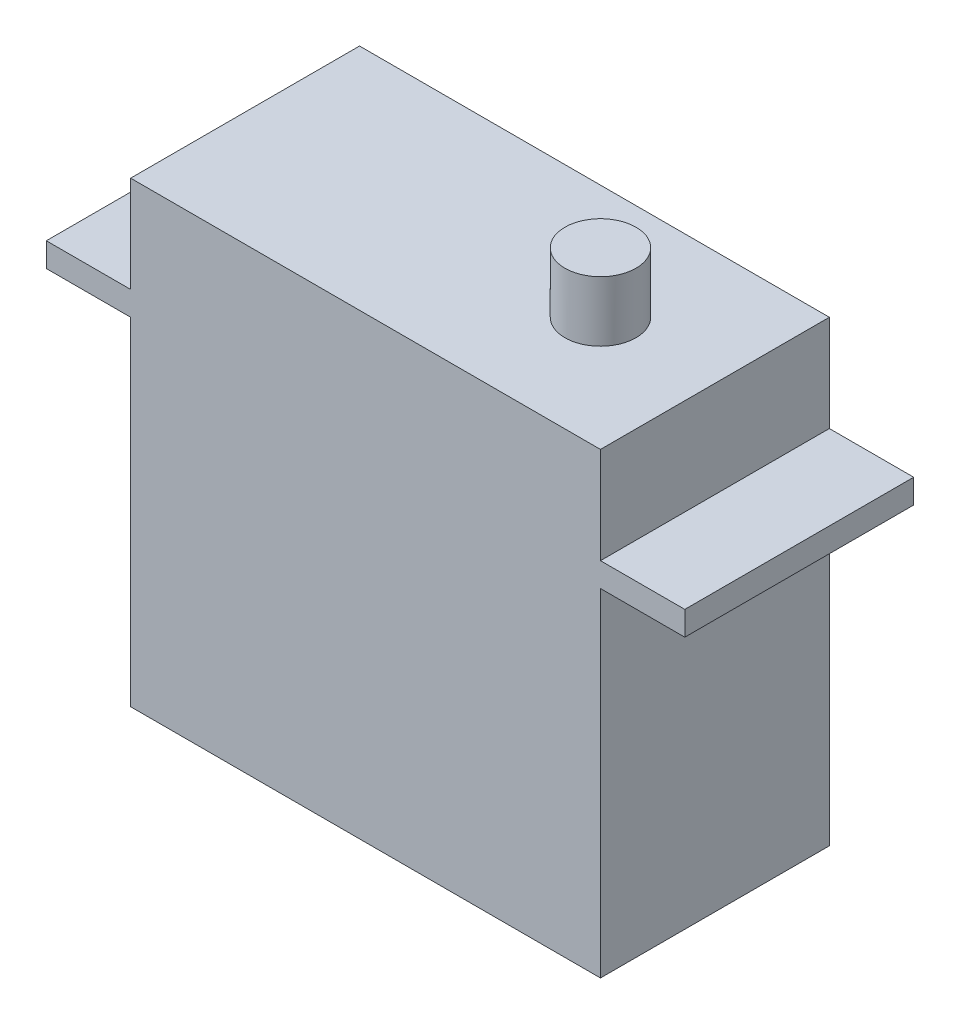
SolidWorks part; units mm, degrees
ref_plane "Plan de face" through (0, 0, 0) normal (0, 0, 1) x (1, 0, 0)
ref_plane "Plan de dessus" through (0, 0, 0) normal (0, 1, 0) x (1, 0, 0)
ref_plane "Plan de droite" through (0, 0, 0) normal (1, 0, 0) x (0, 0, -1)
sketch "Esquisse1" plane through (0, 0, 0) normal (0, 0, 1) x (1, 0, 0)
  line L0 (0, 0) -> (0, 28)
  line L1 (0, 0) -> (39, 0)
  line L2 (0, 28) -> (39, 28)
  line L3 (39, 0) -> (39, 28)
  line L4 (39, 28) -> (0, 28)
  line L5 (39, 28) -> (39, 38)
  line L6 (0, 28) -> (0, 38)
  line L7 (39, 38) -> (0, 38)
  line L8 (39, 28) -> (46, 28)
  line L9 (39, 28) -> (39, 30)
  line L10 (46, 28) -> (46, 30)
  line L11 (39, 30) -> (46, 30)
  line L12 (0, 28) -> (-7, 28)
  line L13 (0, 28) -> (0, 30)
  line L14 (-7, 28) -> (-7, 30)
  line L15 (0, 30) -> (-7, 30)
  point P14 (-0.3418, 28)
  dimension "D1" = 39
  dimension "D2" = 28
  dimension "D3" = 2
  dimension "D4" = 38
  dimension "D5" = 2
  dimension "D6" = 53
extrude "Boss.-Extru.1" add sketch "Esquisse1" along normal blind 19 contours L1 L3 L2 L0 | L5 L7 L6 L2 | L6 L15 L14 L12 | L11 L5 L8 L10 region at (19.5, 14, 0) region at (19.5, 33, 0) region at (-3.5, 29, 0) region at (42.5, 29, 0)
sketch "Esquisse2" plane through (0, 38, 0) normal (0, 1, 0) x (1, 0, 0)
  line L0 (39, -19) -> (0, -19) construction
  line L2 (39, 0) -> (0, 0) construction
  line L3 (39, -19) -> (39, 0) construction
  circle A0 centre (29.5, -9.5) radius 9.5
  circle A1 centre (29.5, -9.5) radius 2.95
  dimension "D1" = 5.9
extrude "Boss.-Extru.2" add sketch "Esquisse2" along normal blind 5 contours A1
